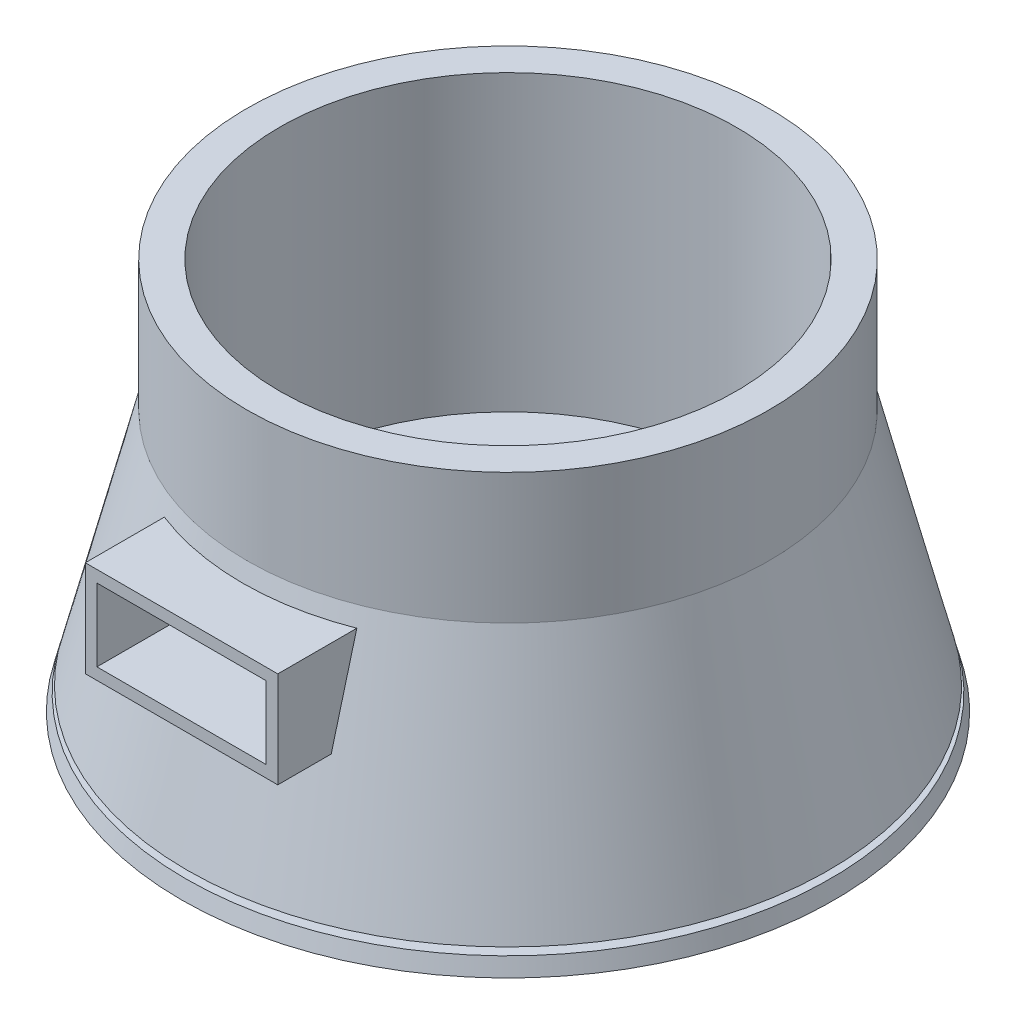
SolidWorks part; units mm, degrees
material "ABS PC"
ref_plane "Front Plane" through (0, 0, 0) normal (0, 0, 1) x (1, 0, 0)
ref_plane "Top Plane" through (0, 0, 0) normal (0, 1, 0) x (1, 0, 0)
ref_plane "Right Plane" through (0, 0, 0) normal (1, 0, 0) x (0, 0, -1)
sketch "Sketch1" plane through (0, 0, 0) normal (0, 1, 0) x (1, 0, 0)
  circle A0 centre (0, 0) radius 25
extrude "Boss-Extrude1" add sketch "Sketch1" along normal blind 30
sketch "Sketch2" plane through (0, 0, 0) normal (0, 0, 1) x (1, 0, 0)
  line L0 (0, 31.4615) -> (0, -1.5389) construction
sketch "Sketch3" plane through (0, 0, 0) normal (0, 0, 1) x (1, 0, 0)
  line L0 (-20, 20) -> (-24.5625, 1.75)
  line L1 (0, 2.5) -> (0, 0)
  line L2 (-25, 30) -> (-20, 30)
  line L3 (-25, 30) -> (-25, 20)
  line L5 (-20, 30) -> (-20, 20)
  line L6 (-25, 0) -> (-25, 20)
  line L7 (-15, 0) -> (-22.5, 0)
  line L10 (-15, 2.5) -> (0, 2.5)
  line L13 (-25, 0) -> (-25, 1.5) construction
  line L14 (-25, 0) -> (25, 0) construction
  line L15 (-22.5, 0) -> (-15, 2.5)
  line L16 (-15, 0) -> (0, 0)
  line L17 (-24.6875, 1.25) -> (-25, 0)
  line L18 (-24.5625, 1.75) -> (-23.75, 1.75)
  line L20 (-24.6875, 1.25) -> (-23.75, 1.25)
  line L21 (-23.75, 1.75) -> (-23.75, 1.25)
  line L22 (-22.5, 0) -> (-25, 0) construction
  line L23 (-23.5, 0) -> (-24, 0)
  line L24 (-24, 0.75) -> (-23.5, 0.75)
  line L25 (-24, 0.75) -> (-24, 0)
  line L27 (-23.5, 0.75) -> (-23.5, 0)
  line L29 (0, 20) -> (-5, 20)
  line L30 (0, 20) -> (0, 2.5)
  line L31 (0, 2.5) -> (-5, 2.5)
  line L32 (-5, 20) -> (-5, 2.5)
  point P5 (0, 0)
  point P21 (-23.75, 0)
revolve "Cut-Revolve1" cut sketch "Sketch3" angle 360 about L0 region at (-22.9222, 19.0897, 0) region at (-9.5, 1.1667, 0) region at (-2.5, 11.25, 0) region at (-23.75, 0.375, 0)
sketch "Sketch6" plane through (0, 0, 0) normal (0, 0, 1) x (1, 0, 0)
  line L1 (-6.48, 17.78) -> (6.48, 17.78)
  line L2 (-6.48, 17.78) -> (-6.48, 12.22)
  line L3 (-6.48, 12.22) -> (6.48, 12.22)
  line L8 (6.48, 17.78) -> (6.48, 12.22)
  line L10 (-7.37, 18.68) -> (7.37, 18.68)
  line L11 (-7.37, 18.68) -> (-7.37, 11.32)
  line L12 (-7.37, 11.32) -> (7.37, 11.32)
  line L13 (7.37, 18.68) -> (7.37, 11.32)
extrude "Boss-Extrude2" add sketch "Sketch6" along normal blind 25 contours L13 L10 L11 L12 region at (0, 18.5152, 0)
sketch "Sketch4" plane through (0, 30, 0) normal (0, 1, 0) x (1, 0, 0)
  circle A0 centre (0, 0) radius 17.5
extrude "Cut-Extrude1" cut sketch "Sketch4" against normal blind 22.5
extrude "Cut-Extrude7" cut sketch "Sketch6<5>" along normal blind 46.5 contours L8 L1 L2 L3 region at (0, 15, 0)
sketch "Sketch6<5>" plane through (0, 0, 0) normal (0, 0, 1) x (1, 0, 0) same geometry as "Sketch6"
